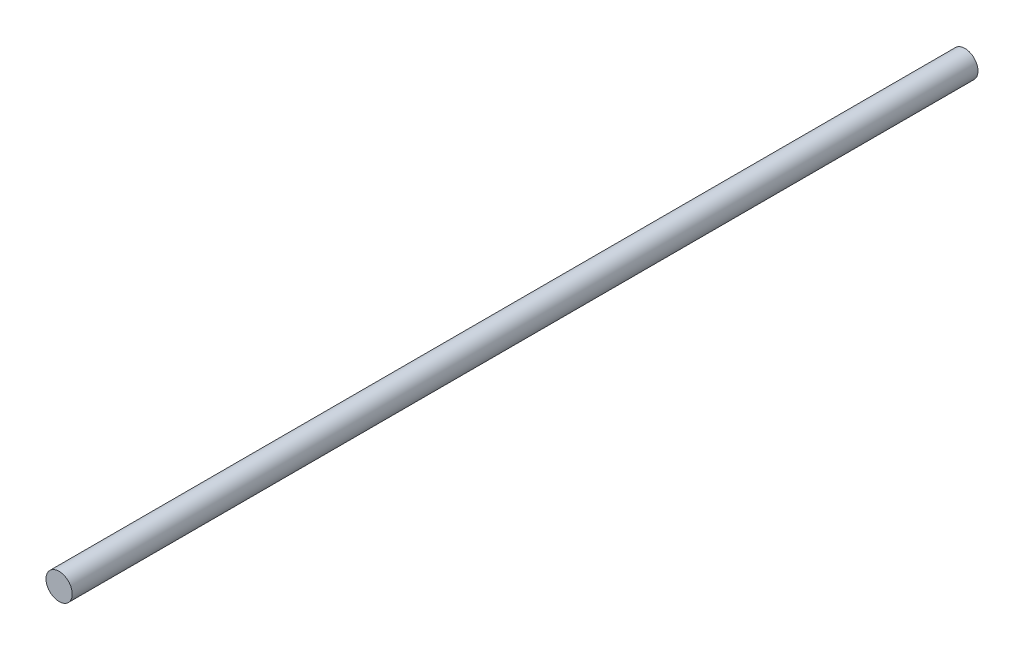
SolidWorks part; units mm, degrees
material "Hexcel AS4C (3000 Filaments)"
ref_plane "Front Plane" through (0, 0, 0) normal (0, 0, 1) x (1, 0, 0)
ref_plane "Top Plane" through (0, 0, 0) normal (0, 1, 0) x (1, 0, 0)
ref_plane "Right Plane" through (0, 0, 0) normal (1, 0, 0) x (0, 0, -1)
sketch "Sketch1" plane through (0, 0, 0) normal (0, 0, 1) x (1, 0, 0)
  circle A0 centre (0, 0) radius 6.35
  dimension "D1" = 12.7
extrude "Boss-Extrude1" add sketch "Sketch1" along normal blind 438.15
